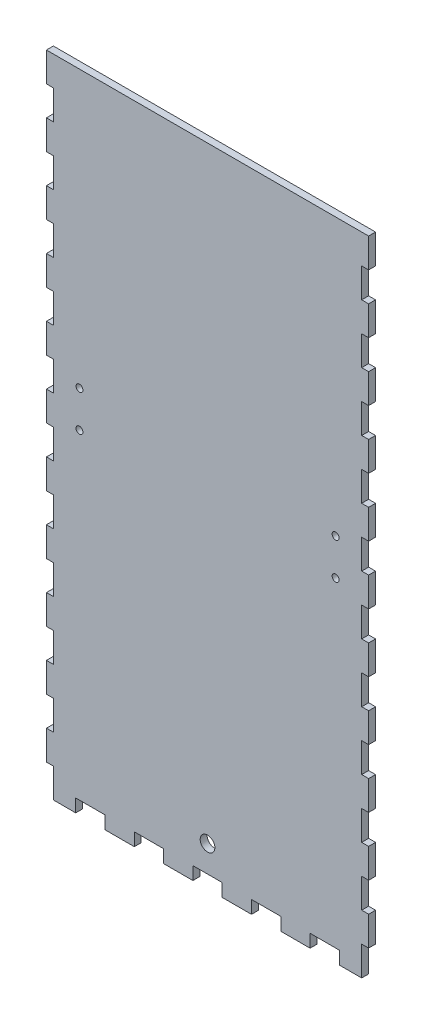
SolidWorks part; units mm, degrees
ref_plane "Front Plane" through (0, 0, 0) normal (0, 0, 1) x (1, 0, 0)
ref_plane "Top Plane" through (0, 0, 0) normal (0, 1, 0) x (1, 0, 0)
ref_plane "Right Plane" through (0, 0, 0) normal (1, 0, 0) x (0, 0, -1)
sketch "Sketch1" plane through (0, 0, 0) normal (0, 0, 1) x (1, 0, 0)
  line L0 (-66.675, 261.112) -> (-66.675, 248.412)
  line L1 (-66.675, 273.812) -> (66.675, 273.812)
  line L2 (-66.675, 273.812) -> (-66.675, 0)
  line L3 (-66.675, 0) -> (66.675, 0)
  line L4 (66.675, 273.812) -> (66.675, 0)
  line L5 (-66.675, 273.812) -> (-69.6722, 273.812)
  line L6 (-66.675, 273.812) -> (-66.675, 261.112)
  line L7 (-66.675, 261.112) -> (-69.6722, 261.112)
  line L8 (-69.6722, 273.812) -> (-69.6722, 261.112)
  line L13 (66.675, 273.812) -> (69.6722, 273.812)
  line L14 (66.675, 273.812) -> (66.675, 261.112)
  line L15 (66.675, 261.112) -> (69.6722, 261.112)
  line L16 (69.6722, 273.812) -> (69.6722, 261.112)
  line L17 (-66.675, 261.112) -> (-69.6722, 261.112)
  line L18 (-69.6722, 261.112) -> (-69.6722, 248.412)
  line L19 (-66.675, 248.412) -> (-69.6722, 248.412)
  line L20 (66.675, 261.112) -> (66.675, 248.412)
  line L21 (66.675, 261.112) -> (69.6722, 261.112)
  line L22 (69.6722, 261.112) -> (69.6722, 248.412)
  line L23 (66.675, 248.412) -> (69.6722, 248.412)
  line L24 (-66.675, 248.412) -> (-66.675, 235.712)
  line L25 (-66.675, 248.412) -> (-69.6722, 248.412)
  line L26 (-69.6722, 248.412) -> (-69.6722, 235.712)
  line L27 (-66.675, 235.712) -> (-69.6722, 235.712)
  line L28 (66.675, 248.412) -> (66.675, 235.712)
  line L29 (66.675, 248.412) -> (69.6722, 248.412)
  line L30 (69.6722, 248.412) -> (69.6722, 235.712)
  line L31 (66.675, 235.712) -> (69.6722, 235.712)
  line L32 (-66.675, 235.712) -> (-66.675, 223.012)
  line L33 (-66.675, 235.712) -> (-69.6722, 235.712)
  line L34 (-69.6722, 235.712) -> (-69.6722, 223.012)
  line L35 (-66.675, 223.012) -> (-69.6722, 223.012)
  line L36 (66.675, 235.712) -> (66.675, 223.012)
  line L37 (66.675, 235.712) -> (69.6722, 235.712)
  line L38 (69.6722, 235.712) -> (69.6722, 223.012)
  line L39 (66.675, 223.012) -> (69.6722, 223.012)
  line L40 (-66.675, 223.012) -> (-66.675, 210.312)
  line L41 (-66.675, 223.012) -> (-69.6722, 223.012)
  line L42 (-69.6722, 223.012) -> (-69.6722, 210.312)
  line L43 (-66.675, 210.312) -> (-69.6722, 210.312)
  line L44 (66.675, 223.012) -> (66.675, 210.312)
  line L45 (66.675, 223.012) -> (69.6722, 223.012)
  line L46 (69.6722, 223.012) -> (69.6722, 210.312)
  line L47 (66.675, 210.312) -> (69.6722, 210.312)
  line L48 (-66.675, 210.312) -> (-66.675, 197.612)
  line L49 (-66.675, 210.312) -> (-69.6722, 210.312)
  line L50 (-69.6722, 210.312) -> (-69.6722, 197.612)
  line L51 (-66.675, 197.612) -> (-69.6722, 197.612)
  line L52 (66.675, 210.312) -> (66.675, 197.612)
  line L53 (66.675, 210.312) -> (69.6722, 210.312)
  line L54 (69.6722, 210.312) -> (69.6722, 197.612)
  line L55 (66.675, 197.612) -> (69.6722, 197.612)
  line L56 (-66.675, 197.612) -> (-66.675, 184.912)
  line L57 (-66.675, 197.612) -> (-69.6722, 197.612)
  line L58 (-69.6722, 197.612) -> (-69.6722, 184.912)
  line L59 (-66.675, 184.912) -> (-69.6722, 184.912)
  line L60 (66.675, 197.612) -> (66.675, 184.912)
  line L61 (66.675, 197.612) -> (69.6722, 197.612)
  line L62 (69.6722, 197.612) -> (69.6722, 184.912)
  line L63 (66.675, 184.912) -> (69.6722, 184.912)
  line L64 (-66.675, 184.912) -> (-66.675, 172.212)
  line L65 (-66.675, 184.912) -> (-69.6722, 184.912)
  line L66 (-69.6722, 184.912) -> (-69.6722, 172.212)
  line L67 (-66.675, 172.212) -> (-69.6722, 172.212)
  line L68 (66.675, 184.912) -> (66.675, 172.212)
  line L69 (66.675, 184.912) -> (69.6722, 184.912)
  line L70 (69.6722, 184.912) -> (69.6722, 172.212)
  line L71 (66.675, 172.212) -> (69.6722, 172.212)
  line L72 (-66.675, 172.212) -> (-66.675, 159.512)
  line L73 (-66.675, 172.212) -> (-69.6722, 172.212)
  line L74 (-69.6722, 172.212) -> (-69.6722, 159.512)
  line L75 (-66.675, 159.512) -> (-69.6722, 159.512)
  line L76 (66.675, 172.212) -> (66.675, 159.512)
  line L77 (66.675, 172.212) -> (69.6722, 172.212)
  line L78 (69.6722, 172.212) -> (69.6722, 159.512)
  line L79 (66.675, 159.512) -> (69.6722, 159.512)
  line L80 (-66.675, 159.512) -> (-66.675, 146.812)
  line L81 (-66.675, 159.512) -> (-69.6722, 159.512)
  line L82 (-69.6722, 159.512) -> (-69.6722, 146.812)
  line L83 (-66.675, 146.812) -> (-69.6722, 146.812)
  line L84 (66.675, 159.512) -> (66.675, 146.812)
  line L85 (66.675, 159.512) -> (69.6722, 159.512)
  line L86 (69.6722, 159.512) -> (69.6722, 146.812)
  line L87 (66.675, 146.812) -> (69.6722, 146.812)
  line L88 (-66.675, 146.812) -> (-66.675, 134.112)
  line L89 (-66.675, 146.812) -> (-69.6722, 146.812)
  line L90 (-69.6722, 146.812) -> (-69.6722, 134.112)
  line L91 (-66.675, 134.112) -> (-69.6722, 134.112)
  line L92 (66.675, 146.812) -> (66.675, 134.112)
  line L93 (66.675, 146.812) -> (69.6722, 146.812)
  line L94 (69.6722, 146.812) -> (69.6722, 134.112)
  line L95 (66.675, 134.112) -> (69.6722, 134.112)
  line L96 (-66.675, 134.112) -> (-66.675, 121.412)
  line L97 (-66.675, 134.112) -> (-69.6722, 134.112)
  line L98 (-69.6722, 134.112) -> (-69.6722, 121.412)
  line L99 (-66.675, 121.412) -> (-69.6722, 121.412)
  line L100 (66.675, 134.112) -> (66.675, 121.412)
  line L101 (66.675, 134.112) -> (69.6722, 134.112)
  line L102 (69.6722, 134.112) -> (69.6722, 121.412)
  line L103 (66.675, 121.412) -> (69.6722, 121.412)
  line L104 (-66.675, 121.412) -> (-66.675, 108.712)
  line L105 (-66.675, 121.412) -> (-69.6722, 121.412)
  line L106 (-69.6722, 121.412) -> (-69.6722, 108.712)
  line L107 (-66.675, 108.712) -> (-69.6722, 108.712)
  line L108 (66.675, 121.412) -> (66.675, 108.712)
  line L109 (66.675, 121.412) -> (69.6722, 121.412)
  line L110 (69.6722, 121.412) -> (69.6722, 108.712)
  line L111 (66.675, 108.712) -> (69.6722, 108.712)
  line L112 (-66.675, 108.712) -> (-66.675, 96.012)
  line L113 (-66.675, 108.712) -> (-69.6722, 108.712)
  line L114 (-69.6722, 108.712) -> (-69.6722, 96.012)
  line L115 (-66.675, 96.012) -> (-69.6722, 96.012)
  line L116 (66.675, 108.712) -> (66.675, 96.012)
  line L117 (66.675, 108.712) -> (69.6722, 108.712)
  line L118 (69.6722, 108.712) -> (69.6722, 96.012)
  line L119 (66.675, 96.012) -> (69.6722, 96.012)
  line L120 (-66.675, 96.012) -> (-66.675, 83.312)
  line L121 (-66.675, 96.012) -> (-69.6722, 96.012)
  line L122 (-69.6722, 96.012) -> (-69.6722, 83.312)
  line L123 (-66.675, 83.312) -> (-69.6722, 83.312)
  line L124 (66.675, 96.012) -> (66.675, 83.312)
  line L125 (66.675, 96.012) -> (69.6722, 96.012)
  line L126 (69.6722, 96.012) -> (69.6722, 83.312)
  line L127 (66.675, 83.312) -> (69.6722, 83.312)
  line L128 (-66.675, 83.312) -> (-66.675, 70.612)
  line L129 (-66.675, 83.312) -> (-69.6722, 83.312)
  line L130 (-69.6722, 83.312) -> (-69.6722, 70.612)
  line L131 (-66.675, 70.612) -> (-69.6722, 70.612)
  line L132 (66.675, 83.312) -> (66.675, 70.612)
  line L133 (66.675, 83.312) -> (69.6722, 83.312)
  line L134 (69.6722, 83.312) -> (69.6722, 70.612)
  line L135 (66.675, 70.612) -> (69.6722, 70.612)
  line L136 (-66.675, 70.612) -> (-66.675, 57.912)
  line L137 (-66.675, 70.612) -> (-69.6722, 70.612)
  line L138 (-69.6722, 70.612) -> (-69.6722, 57.912)
  line L139 (-66.675, 57.912) -> (-69.6722, 57.912)
  line L140 (66.675, 70.612) -> (66.675, 57.912)
  line L141 (66.675, 70.612) -> (69.6722, 70.612)
  line L142 (69.6722, 70.612) -> (69.6722, 57.912)
  line L143 (66.675, 57.912) -> (69.6722, 57.912)
  line L144 (-66.675, 57.912) -> (-66.675, 45.212)
  line L145 (-66.675, 57.912) -> (-69.6722, 57.912)
  line L146 (-69.6722, 57.912) -> (-69.6722, 45.212)
  line L147 (-66.675, 45.212) -> (-69.6722, 45.212)
  line L148 (66.675, 57.912) -> (66.675, 45.212)
  line L149 (66.675, 57.912) -> (69.6722, 57.912)
  line L150 (69.6722, 57.912) -> (69.6722, 45.212)
  line L151 (66.675, 45.212) -> (69.6722, 45.212)
  line L152 (-66.675, 45.212) -> (-66.675, 32.512)
  line L153 (-66.675, 45.212) -> (-69.6722, 45.212)
  line L154 (-69.6722, 45.212) -> (-69.6722, 32.512)
  line L155 (-66.675, 32.512) -> (-69.6722, 32.512)
  line L156 (66.675, 45.212) -> (66.675, 32.512)
  line L157 (66.675, 45.212) -> (69.6722, 45.212)
  line L158 (69.6722, 45.212) -> (69.6722, 32.512)
  line L159 (66.675, 32.512) -> (69.6722, 32.512)
  line L160 (-66.675, 32.512) -> (-66.675, 19.812)
  line L161 (-66.675, 32.512) -> (-69.6722, 32.512)
  line L162 (-69.6722, 32.512) -> (-69.6722, 19.812)
  line L163 (-66.675, 19.812) -> (-69.6722, 19.812)
  line L164 (66.675, 32.512) -> (66.675, 19.812)
  line L165 (66.675, 32.512) -> (69.6722, 32.512)
  line L166 (69.6722, 32.512) -> (69.6722, 19.812)
  line L167 (66.675, 19.812) -> (69.6722, 19.812)
  line L168 (-66.675, 19.812) -> (-66.675, 7.112)
  line L169 (-66.675, 19.812) -> (-69.6722, 19.812)
  line L170 (-69.6722, 19.812) -> (-69.6722, 7.112)
  line L171 (-66.675, 7.112) -> (-69.6722, 7.112)
  line L172 (66.675, 19.812) -> (66.675, 7.112)
  line L173 (66.675, 19.812) -> (69.6722, 19.812)
  line L174 (69.6722, 19.812) -> (69.6722, 7.112)
  line L175 (66.675, 7.112) -> (69.6722, 7.112)
  line L176 (-66.675, 7.112) -> (-66.675, -5.588)
  line L177 (-66.675, 7.112) -> (-69.6722, 7.112)
  line L178 (-69.6722, 7.112) -> (-69.6722, -5.588)
  line L179 (-66.675, -5.588) -> (-69.6722, -5.588)
  line L180 (66.675, 7.112) -> (66.675, -5.588)
  line L181 (66.675, 7.112) -> (69.6722, 7.112)
  line L182 (69.6722, 7.112) -> (69.6722, -5.588)
  line L183 (66.675, -5.588) -> (69.6722, -5.588)
  line L184 (-57.0045, 0) -> (-57.0045, -5.588)
  line L185 (-69.6722, 0) -> (-57.0045, 0)
  line L186 (-69.6722, 0) -> (-69.6722, -5.588)
  line L187 (-69.6722, -5.588) -> (-57.0045, -5.588)
  line L188 (-57.0045, 0) -> (-57.0045, -5.588)
  line L189 (-57.0045, 0) -> (-44.3369, 0)
  line L190 (-44.3369, 0) -> (-44.3369, -5.588)
  line L191 (-57.0045, -5.588) -> (-44.3369, -5.588)
  line L192 (-44.3369, 0) -> (-44.3369, -5.588)
  line L193 (-44.3369, 0) -> (-31.6692, 0)
  line L194 (-31.6692, 0) -> (-31.6692, -5.588)
  line L195 (-44.3369, -5.588) -> (-31.6692, -5.588)
  line L196 (-31.6692, 0) -> (-31.6692, -5.588)
  line L197 (-31.6692, 0) -> (-19.0015, 0)
  line L198 (-19.0015, 0) -> (-19.0015, -5.588)
  line L199 (-31.6692, -5.588) -> (-19.0015, -5.588)
  line L200 (-19.0015, 0) -> (-19.0015, -5.588)
  line L201 (-19.0015, 0) -> (-6.3338, 0)
  line L202 (-6.3338, 0) -> (-6.3338, -5.588)
  line L203 (-19.0015, -5.588) -> (-6.3338, -5.588)
  line L204 (-6.3338, 0) -> (-6.3338, -5.588)
  line L205 (-6.3338, 0) -> (6.3338, 0)
  line L206 (6.3338, 0) -> (6.3338, -5.588)
  line L207 (-6.3338, -5.588) -> (6.3338, -5.588)
  line L208 (6.3338, 0) -> (6.3338, -5.588)
  line L209 (6.3338, 0) -> (19.0015, 0)
  line L210 (19.0015, 0) -> (19.0015, -5.588)
  line L211 (6.3338, -5.588) -> (19.0015, -5.588)
  line L212 (19.0015, 0) -> (19.0015, -5.588)
  line L213 (19.0015, 0) -> (31.6692, 0)
  line L214 (31.6692, 0) -> (31.6692, -5.588)
  line L215 (19.0015, -5.588) -> (31.6692, -5.588)
  line L216 (31.6692, 0) -> (31.6692, -5.588)
  line L217 (31.6692, 0) -> (44.3369, 0)
  line L218 (44.3369, 0) -> (44.3369, -5.588)
  line L219 (31.6692, -5.588) -> (44.3369, -5.588)
  line L220 (44.3369, 0) -> (44.3369, -5.588)
  line L221 (44.3369, 0) -> (57.0045, 0)
  line L222 (57.0045, 0) -> (57.0045, -5.588)
  line L223 (44.3369, -5.588) -> (57.0045, -5.588)
  line L224 (57.0045, 0) -> (57.0045, -5.588)
  line L225 (57.0045, 0) -> (69.6722, 0)
  line L226 (69.6722, 0) -> (69.6722, -5.588)
  line L227 (57.0045, -5.588) -> (69.6722, -5.588)
  point P4 (0, 0)
  dimension "D1" = 133.35
  dimension "D2" = 273.812
  dimension "D3" = 139.3444
  dimension "D6" = 279.4
  dimension "D7" = 12.7
  dimension "D8" = 12.6677
  dimension "D4" = 22
  dimension "D5" = 11
extrude "Boss-Extrude1" add sketch "Sketch1" along normal blind 2.9972 contours L4 L1 L2 L0 L3 | L171 L2 L163 L170 | L155 L2 L147 L154 | L139 L2 L131 L138 | L123 L2 L115 L122 | L176 L187 L184 L3 | L190 L195 L194 L3 | L198 L203 L202 L3 | L206 L211 L210 L3 | L214 L219 L218 L3 | L222 L227 L180 L3 | L4 L175 L174 L167 | L4 L159 L158 L151 | L4 L143 L142 L135 | L4 L127 L126 L119 | L4 L111 L110 L103 | L107 L2 L99 L106 | L91 L2 L83 L90 | L75 L2 L67 L74 | L59 L2 L51 L58 | L43 L2 L35 L42 | L27 L2 L19 L26 | L5 L8 L7 L2 | L4 L95 L94 L87 | L4 L79 L78 L71 | L4 L63 L62 L55 | L4 L47 L46 L39 | L4 L31 L30 L23 | L16 L13 L4 L15 region at (0, 136.906, 0) region at (-68.1736, 267.462, 0) region at (-68.1736, 242.062, 0) region at (68.1736, 267.462, 0) region at (-68.1736, 216.662, 0) region at (68.1736, 242.062, 0) region at (-68.1736, 191.262, 0) region at (68.1736, 216.662, 0) region at (-68.1736, 165.862, 0) region at (68.1736, 191.262, 0) region at (-68.1736, 140.462, 0) region at (68.1736, 165.862, 0) region at (-68.1736, 115.062, 0) region at (68.1736, 140.462, 0) region at (-68.1736, 89.662, 0) region at (68.1736, 115.062, 0) region at (-68.1736, 64.262, 0) region at (68.1736, 89.662, 0) region at (-68.1736, 38.862, 0) region at (68.1736, 64.262, 0) region at (-68.1736, 13.462, 0) region at (68.1736, 38.862, 0) region at (-61.8398, -2.794, 0) region at (68.1736, 13.462, 0) region at (-38.003, -2.794, 0) region at (61.8398, -2.794, 0) region at (-12.6677, -2.794, 0) region at (38.003, -2.794, 0) region at (12.6677, -2.794, 0)
sketch "Sketch2" plane through (0, 0, 2.9972) normal (0, 0, 1) x (1, 0, 0)
  circle A0 centre (0, 11.43) radius 3.175
  dimension "D2" = 6.35
  dimension "D1" = 11.43
extrude "Cut-Extrude1" cut sketch "Sketch2" against normal through all
sketch "Sketch3" plane through (0, 0, 2.9972) normal (0, 0, 1) x (1, 0, 0)
  line L0 (-55.3847, 154.305) -> (-55.3847, 138.557) construction
  line L1 (55.3847, 154.305) -> (55.3847, 138.557) construction
  line L2 (-55.3847, 146.431) -> (55.3847, 146.431) construction
  line L3 (-57.0045, 0) -> (-44.3369, 0) construction
  line L5 (-69.6722, 146.812) -> (-69.6722, 134.112) construction
  circle A0 centre (-55.3847, 154.305) radius 1.5
  circle A1 centre (-55.3847, 138.557) radius 1.5
  circle A2 centre (55.3847, 154.305) radius 1.5
  circle A3 centre (55.3847, 138.557) radius 1.5
  point P10 (0, 146.431)
  dimension "D2" = 3
  dimension "D3" = 138.557
  dimension "D4" = 14.2875
  dimension "D1" = 15.748
extrude "Cut-Extrude2" cut sketch "Sketch3" against normal through all
equation "\"bottomThickness\"= .220in"
equation "\"wallThickness\"= .118in"
equation "\"D3@Sketch1\"=2*\"wallThickness\"+5.25"
equation "\"D6@Sketch1\"=\"bottomThickness\"+10.78"
equation "\"D7@Sketch1\"=\"D6@Sketch1\"/\"D4@Sketch1\""
equation "\"D8@Sketch1\"=\"D3@Sketch1\"/\"D5@Sketch1\""
equation "\"D1@Boss-Extrude1\"=\"wallThickness\""
